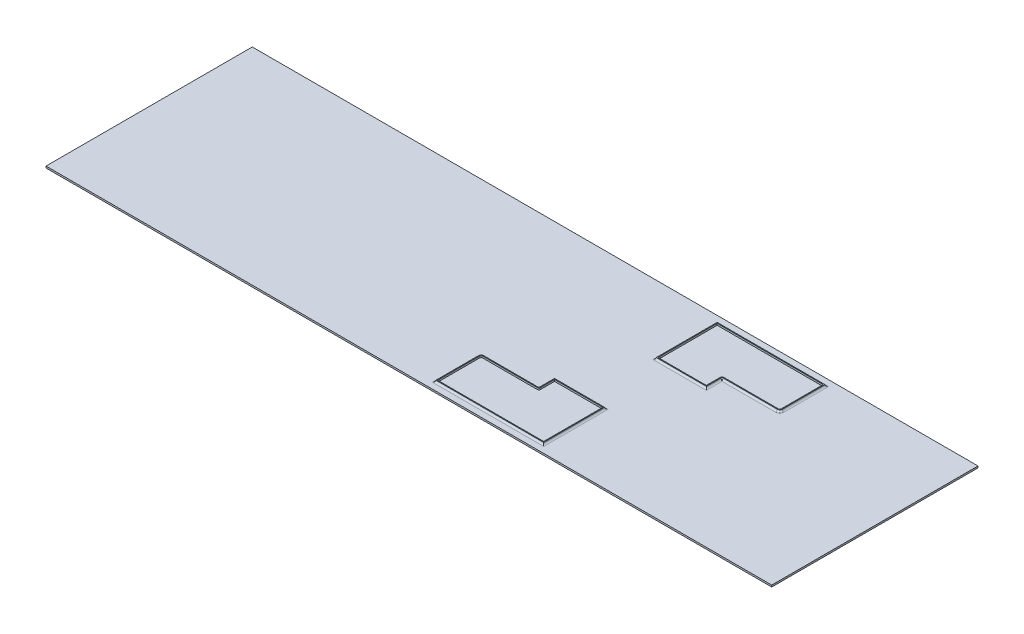
SolidWorks part; units mm, degrees
ref_plane "Front Plane" through (0, 0, 0) normal (0, 0, 1) x (1, 0, 0)
ref_plane "Top Plane" through (0, 0, 0) normal (0, 1, 0) x (1, 0, 0)
ref_plane "Right Plane" through (0, 0, 0) normal (1, 0, 0) x (0, 0, -1)
sketch "Sketch1" plane through (0, 287.2352, 0) normal (0, -1, 0) x (1, 0, 0)
  line L0 (295.5772, 2393.1549) -> (-319.3738, 2393.1549) construction
  line L1 (-2540.4228, 2443.1549) -> (1668.0972, 2443.1549)
  line L2 (-2540.4228, 2443.1549) -> (-2540.4228, 1246.9486)
  line L3 (-2540.4228, 1246.9486) -> (1668.0972, 1246.9486)
  line L4 (1668.0972, 2443.1549) -> (1668.0972, 1246.9486)
  line L5 (205.5772, 1296.9486) -> (820.5282, 1296.9486) construction
  line L6 (1175.5772, 2009.9506) -> (1175.5772, 1679.9506) construction
  line L7 (-674.4228, 2014.9506) -> (-674.4228, 1674.9506) construction
  dimension "D1" = 50
  dimension "D2" = 50
  dimension "D3" = 492.52
  dimension "D4" = 1866
extrude "Bottom plate" add sketch "Sketch1" along normal blind 10
sketch "Sketch3" plane through (0, 287.2352, 0) normal (0, 1, 0) x (1, 0, 0)
  line L0 (15.5772, -2050.1529) -> (295.5772, -2050.1529) construction
  line L1 (15.5772, -2131.0779) -> (15.5772, -2050.1529) construction
  line L2 (-309.3738, -2141.0779) -> (5.5772, -2141.0779) construction
  line L3 (295.5772, -2050.1529) -> (295.5772, -2393.1549) construction
  line L4 (-319.3738, -2393.1549) -> (-319.3738, -2151.0779) construction
  line L5 (295.5772, -2393.1549) -> (-319.3738, -2393.1549) construction
  line L6 (15.5772, -2050.1529) -> (295.5772, -2050.1529)
  line L7 (15.5772, -2131.0779) -> (15.5772, -2050.1529)
  line L8 (-309.3738, -2141.0779) -> (5.5772, -2141.0779)
  line L9 (295.5772, -2050.1529) -> (295.5772, -2393.1549)
  line L10 (-319.3738, -2393.1549) -> (-319.3738, -2151.0779)
  line L11 (295.5772, -2393.1549) -> (-319.3738, -2393.1549)
  line L12 (205.5772, -1639.9506) -> (205.5772, -1296.9486) construction
  line L13 (205.5772, -1296.9486) -> (820.5282, -1296.9486) construction
  line L14 (820.5282, -1296.9486) -> (820.5282, -1539.0256) construction
  line L15 (810.5282, -1549.0256) -> (495.5772, -1549.0256) construction
  line L16 (485.5772, -1559.0256) -> (485.5772, -1639.9506) construction
  line L17 (485.5772, -1639.9506) -> (205.5772, -1639.9506) construction
  line L18 (205.5772, -1639.9506) -> (205.5772, -1296.9486)
  line L19 (205.5772, -1296.9486) -> (820.5282, -1296.9486)
  line L20 (820.5282, -1296.9486) -> (820.5282, -1539.0256)
  line L21 (810.5282, -1549.0256) -> (495.5772, -1549.0256)
  line L22 (485.5772, -1559.0256) -> (485.5772, -1639.9506)
  line L23 (485.5772, -1639.9506) -> (205.5772, -1639.9506)
  line L24 (200.5772, -1644.9506) -> (200.5772, -1291.9486)
  line L25 (200.5772, -1291.9486) -> (825.5282, -1291.9486)
  line L26 (825.5282, -1291.9486) -> (825.5282, -1539.0256)
  line L27 (810.5282, -1554.0256) -> (495.5772, -1554.0256)
  line L28 (490.5772, -1559.0256) -> (490.5772, -1644.9506)
  line L29 (490.5772, -1644.9506) -> (200.5772, -1644.9506)
  line L30 (10.5772, -2045.1529) -> (300.5772, -2045.1529)
  line L31 (300.5772, -2045.1529) -> (300.5772, -2398.1549)
  line L32 (300.5772, -2398.1549) -> (-324.3738, -2398.1549)
  line L33 (-324.3738, -2398.1549) -> (-324.3738, -2151.0779)
  line L34 (-309.3738, -2136.0779) -> (5.5772, -2136.0779)
  line L35 (10.5772, -2131.0779) -> (10.5772, -2045.1529)
  arc A0 (5.5772, -2141.0779) -> (15.5772, -2131.0779) centre (5.5772, -2131.0779) ccw construction
  arc A1 (-309.3738, -2141.0779) -> (-319.3738, -2151.0779) centre (-309.3738, -2151.0779) ccw construction
  arc A2 (5.5772, -2141.0779) -> (15.5772, -2131.0779) centre (5.5772, -2131.0779) ccw
  arc A3 (-309.3738, -2141.0779) -> (-319.3738, -2151.0779) centre (-309.3738, -2151.0779) ccw
  arc A4 (810.5282, -1549.0256) -> (820.5282, -1539.0256) centre (810.5282, -1539.0256) ccw construction
  arc A5 (495.5772, -1549.0256) -> (485.5772, -1559.0256) centre (495.5772, -1559.0256) ccw construction
  arc A6 (810.5282, -1549.0256) -> (820.5282, -1539.0256) centre (810.5282, -1539.0256) ccw
  arc A7 (495.5772, -1549.0256) -> (485.5772, -1559.0256) centre (495.5772, -1559.0256) ccw
  arc A8 (810.5282, -1554.0256) -> (825.5282, -1539.0256) centre (810.5282, -1539.0256) ccw
  arc A9 (495.5772, -1554.0256) -> (490.5772, -1559.0256) centre (495.5772, -1559.0256) ccw
  arc A10 (-309.3738, -2136.0779) -> (-324.3738, -2151.0779) centre (-309.3738, -2151.0779) ccw
  arc A11 (5.5772, -2136.0779) -> (10.5772, -2131.0779) centre (5.5772, -2131.0779) ccw
  dimension "D1" = 5
extrude "Elevator mechanism outlines" add sketch "Sketch3" along normal blind 10
fillet "Outline fillets" radius 10 16 edges at (825.5282, 287.2352, 1415.4871) (821.1348, 287.2352, 1549.6322) (653.0527, 287.2352, 1554.0256) (492.0417, 287.2352, 1555.4901) (10.5772, 287.2352, 2088.1154) (9.1127, 287.2352, 2134.6135) (-324.3738, 287.2352, 2274.6164) (-319.9804, 287.2352, 2140.4713) (490.5772, 287.2352, 1601.9881) (345.5772, 287.2352, 1644.9506) (200.5772, 287.2352, 1468.4496) (513.0527, 287.2352, 1291.9486) (-151.8983, 287.2352, 2136.0779) (155.5772, 287.2352, 2045.1529) (300.5772, 287.2352, 2221.6539) (-11.8983, 287.2352, 2398.1549)
